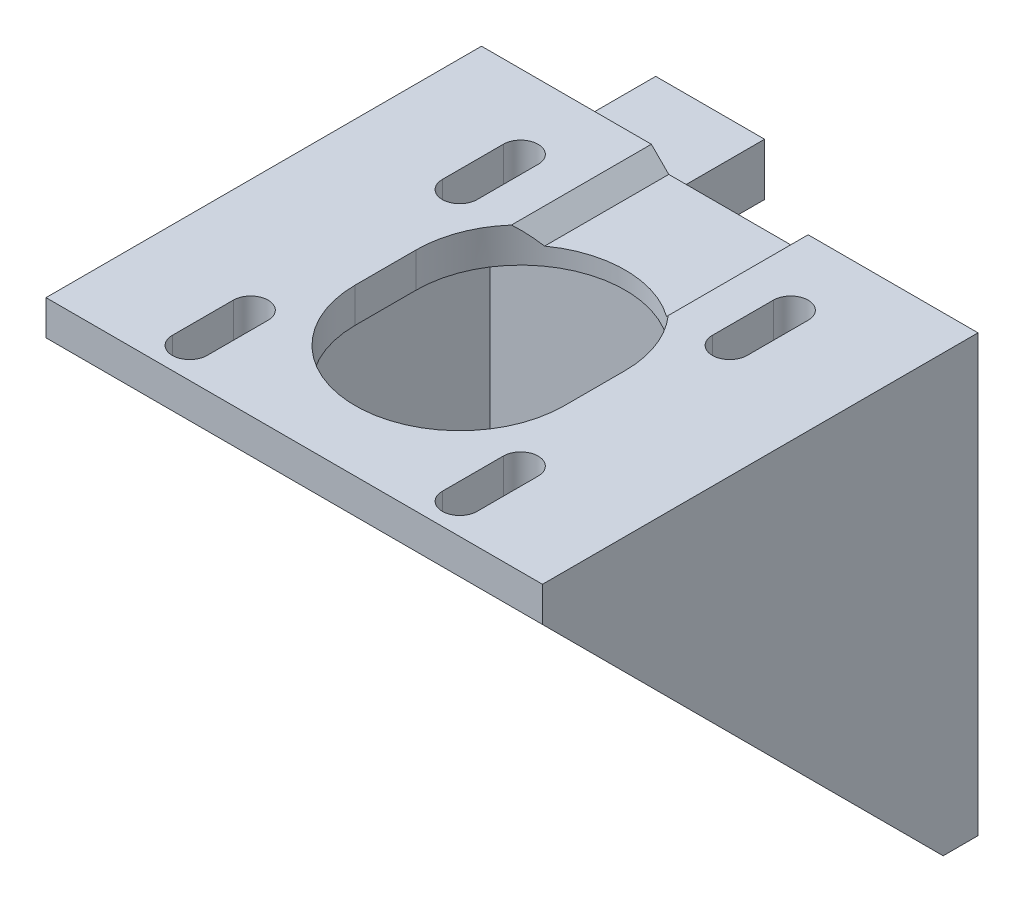
SolidWorks part; units mm, degrees
ref_plane "Front Plane" through (0, 0, 0) normal (0, 0, 1) x (1, 0, 0)
ref_plane "Top Plane" through (0, 0, 0) normal (0, 1, 0) x (1, 0, 0)
ref_plane "Right Plane" through (0, 0, 0) normal (1, 0, 0) x (0, 0, -1)
sketch "Sketch1" plane through (0, 0, 0) normal (0, 0, 1) x (1, 0, 0)
  line L1 (-28.5, 25) -> (28.5, 25)
  line L2 (-28.5, 25) -> (-28.5, -25)
  line L3 (-28.5, -25) -> (28.5, -25)
  line L4 (28.5, 25) -> (28.5, -25)
  line L5 (-28.5, 25) -> (28.5, -25) construction
  line L6 (-28.5, -25) -> (28.5, 25) construction
  point P0 (0, 0)
  dimension "D1" = 57
  dimension "D2" = 50
extrude "Boss-Extrude1" add sketch "Sketch1" along normal blind 50
sketch "Sketch2" plane through (0, 0, 50) normal (0, 0, 1) x (1, 0, 0)
  line L0 (-28.5, -25) -> (28.5, -25) construction
  line L1 (-24.5, -25) -> (24.5, -25)
  line L2 (-24.5, -25) -> (-24.5, 21)
  line L3 (-24.5, 21) -> (24.5, 21)
  line L4 (24.5, -25) -> (24.5, 21)
  line L5 (-28.5, 25) -> (-28.5, -25) construction
  line L6 (28.5, -25) -> (28.5, 25) construction
  line L7 (28.5, 25) -> (-28.5, 25) construction
  dimension "D1" = 4
  dimension "D2" = 4
  dimension "D3" = 4
extrude "Cut-Extrude1" cut sketch "Sketch2" against normal blind 47
chamfer "Chamfer1" distance 46 angle 45 2 edges at (26.5, -25, 50) (-26.5, -25, 50)
sketch "Sketch3" plane through (0, 25, 0) normal (0, 1, 0) x (1, 0, 0)
  line L0 (28.5, 0) -> (-28.5, 0) construction
  line L1 (-15.5, -8.5) -> (-15.5, -15.5) construction
  line L2 (-13.5, -8.5) -> (-13.5, -15.5)
  line L3 (-17.5, -8.5) -> (-17.5, -15.5)
  line L4 (-15.5, -39.5) -> (-15.5, -46.5) construction
  line L5 (-13.5, -39.5) -> (-13.5, -46.5)
  line L6 (-17.5, -39.5) -> (-17.5, -46.5)
  line L7 (15.5, -39.5) -> (15.5, -46.5) construction
  line L8 (17.5, -39.5) -> (17.5, -46.5)
  line L9 (13.5, -39.5) -> (13.5, -46.5)
  line L10 (15.5, -8.5) -> (15.5, -15.5) construction
  line L11 (17.5, -8.5) -> (17.5, -15.5)
  line L12 (13.5, -8.5) -> (13.5, -15.5)
  line L13 (0, -24) -> (0, -31) construction
  line L14 (12, -24) -> (12, -31)
  line L15 (-12, -24) -> (-12, -31)
  arc A0 (-13.5, -8.5) -> (-17.5, -8.5) centre (-15.5, -8.5) ccw
  arc A1 (-17.5, -15.5) -> (-13.5, -15.5) centre (-15.5, -15.5) ccw
  arc A2 (-13.5, -39.5) -> (-17.5, -39.5) centre (-15.5, -39.5) ccw
  arc A3 (-17.5, -46.5) -> (-13.5, -46.5) centre (-15.5, -46.5) ccw
  arc A4 (17.5, -39.5) -> (13.5, -39.5) centre (15.5, -39.5) ccw
  circle A5 centre (0, -24) radius 12 construction
  circle A6 centre (-15.5, -8.5) radius 2 construction
  circle A7 centre (15.5, -8.5) radius 2 construction
  circle A8 centre (15.5, -39.5) radius 2 construction
  circle A9 centre (-15.5, -39.5) radius 2 construction
  arc A10 (13.5, -46.5) -> (17.5, -46.5) centre (15.5, -46.5) ccw
  arc A11 (17.5, -8.5) -> (13.5, -8.5) centre (15.5, -8.5) ccw
  arc A12 (13.5, -15.5) -> (17.5, -15.5) centre (15.5, -15.5) ccw
  arc A13 (12, -24) -> (-12, -24) centre (0, -24) ccw
  arc A14 (-12, -31) -> (12, -31) centre (0, -31) ccw
  point P5 (-15.5, -12)
  point P18 (-15.5, -43)
  point P25 (15.5, -43)
  point P31 (15.5, -12)
  point P37 (0, -27.5)
  dimension "D1" = 24
  dimension "D2" = 31
  dimension "D7" = 4
  dimension "D3" = 31
  dimension "D4" = 31
  dimension "D5" = 8.5
  dimension "D6" = 15.5
  dimension "D8" = 24
  dimension "D9" = 7
extrude "Cut-Extrude2" cut sketch "Sketch3" against normal blind 10
sketch "Sketch4" plane through (0, 0, 0) normal (0, 0, -1) x (-1, 0, 0)
  line L0 (28.5, 25) -> (28.5, -25) construction
  line L1 (28.5, 12) -> (16, 12)
  line L2 (28.5, 12) -> (28.5, 6)
  line L3 (28.5, 6) -> (16, 6)
  line L4 (16, 12) -> (16, 6)
  line L5 (-29, 6) -> (431, 6) construction
  line L7 (16, 6) -> (16, 12) construction
  dimension "D1" = 6
extrude "Boss-Extrude2" add sketch "Sketch4" along normal blind 20
sketch "Sketch5" plane through (0, 0, 3) normal (0, 0, 1) x (1, 0, 0)
  line L0 (-24.5, -25) -> (24.5, -25) construction
  line L1 (29, -14) -> (29, -374) construction
  circle A0 centre (19, -21) radius 2.25
  dimension "D1" = 4.5
  dimension "D2" = 4
  dimension "D3" = 10
sketch "Sketch6" plane through (0, 12, 0) normal (0, 1, 0) x (1, 0, 0)
  line L0 (-28.5, 20) -> (-16, 20) construction
  circle A0 centre (-22.25, 10) radius 2.25
  point P6 (-22.25, 20)
  dimension "D2" = 4.5
  dimension "D1" = 10
extrude "Cut-Extrude3" cut sketch "Sketch6" against normal blind 20
extrude "Cut-Extrude4" cut sketch "Sketch5" against normal blind 20
pattern_linear "LPattern1" count 2 spacing 26 along (0, -1, 0) of "Cut-Extrude3", "Boss-Extrude2"
chamfer "Chamfer2" distance 4 angle 45 2 edges at (-22.25, -20, 0) (-22.25, 12, 0)
sketch "Sketch7" plane through (0, 25, 0) normal (0, 1, 0) x (1, 0, 0)
  line L0 (28.5, 0) -> (-28.5, 0) construction
  line L1 (-9, 0) -> (9, 0)
  line L2 (-9, 0) -> (-9, -18.7178)
  line L3 (-9, -18.7178) -> (9, -18.7178)
  line L4 (9, 0) -> (9, -18.7178)
  dimension "D1" = 18
  dimension "D2" = 9
extrude "Cut-Extrude5" cut sketch "Sketch7" against normal blind 2
chamfer "Chamfer3" distance 2 angle 45 2 edges at (9, 23, 8.0314) (-9, 23, 8.0314)
